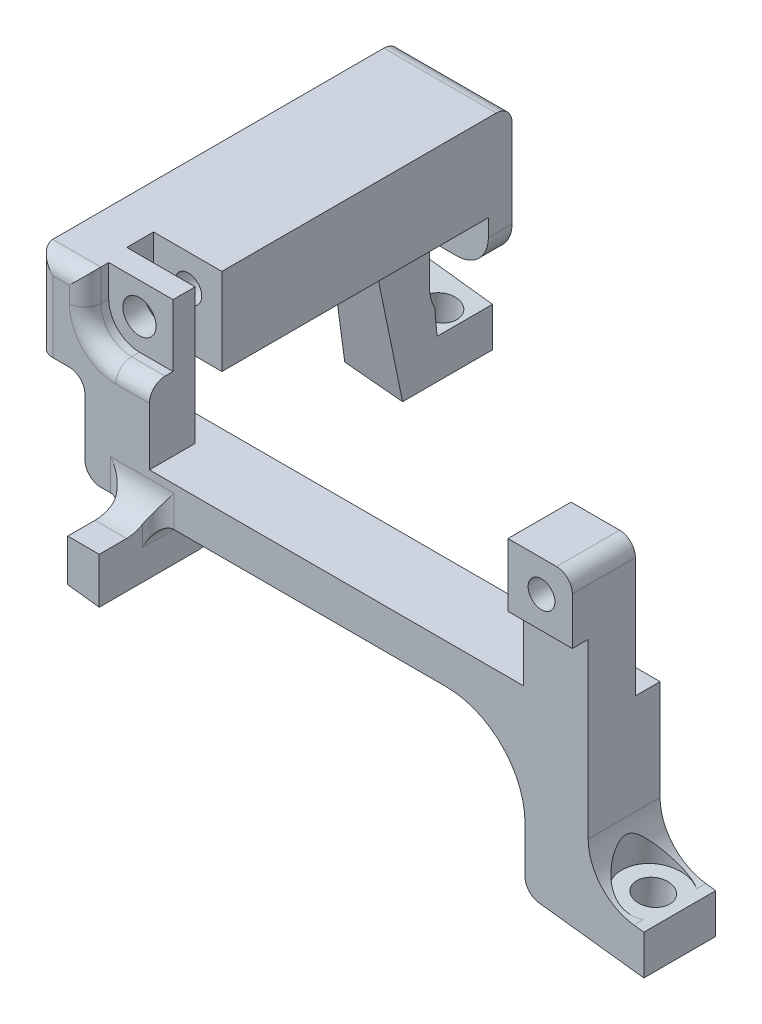
SolidWorks part; units mm, degrees
ref_plane "Front" through (0, 0, 0) normal (0, 0, 1) x (1, 0, 0)
ref_plane "Top" through (0, 0, 0) normal (0, 1, 0) x (1, 0, 0)
ref_plane "Right" through (0, 0, 0) normal (1, 0, 0) x (0, 0, -1)
sketch "Sketch1" plane through (0, 0, 0) normal (0, 0, 1) x (1, 0, 0)
  line L0 (14, 0) -> (-14, 0) construction
  line L1 (0, 0) -> (0, 9.8285) construction
  line L2 (-14, -1) -> (-16, -1)
  line L3 (-16, -1) -> (-16, -5)
  line L4 (-14.5, -6.5) -> (-10.625, -6.5)
  line L5 (-10.625, -6.5) -> (-11.575, 0)
  line L6 (-11.575, 0) -> (-10.625, 6.5)
  line L7 (-10.625, 6.5) -> (-14.5, 6.5)
  line L8 (-16, 5) -> (-16, 1)
  line L9 (-16, 1) -> (-14, 1)
  line L10 (14, 1) -> (16, 1)
  line L11 (16, 1) -> (16, 5)
  line L12 (14.5, 6.5) -> (11.575, 6.5)
  line L13 (11.575, 6.5) -> (11.575, -6.5)
  line L14 (11.575, -6.5) -> (14.5, -6.5)
  line L15 (16, -5) -> (16, -1)
  line L16 (16, -1) -> (14, -1)
  circle A0 centre (-14, -3.5) radius 1.2
  arc A1 (-14, -1) -> (-14, 1) centre (-14, 0) ccw
  arc A2 (-16, -5) -> (-14.5, -6.5) centre (-14.5, -5) ccw
  arc A3 (-14.5, 6.5) -> (-16, 5) centre (-14.5, 5) ccw
  arc A4 (14, 1) -> (14, -1) centre (14, 0) ccw
  arc A5 (16, 5) -> (14.5, 6.5) centre (14.5, 5) ccw
  arc A6 (14.5, -6.5) -> (16, -5) centre (14.5, -5) ccw
  circle A7 centre (-14, 3.5) radius 1.2
  circle A8 centre (14, 3.5) radius 1.2
  circle A9 centre (14, -3.5) radius 1.2
sketch "Sketch2" plane through (0, 0, 0) normal (0, 0, 1) x (1, 0, 0)
  line L0 (0, 9.8285) -> (0, 0) construction
  line L1 (0, 0) -> (7.7633, 0) construction
  line L2 (14, 0) -> (-14, 0) construction
  line L3 (11.8723, 2) -> (11.8723, -6.6)
  line L4 (11.8723, 2) -> (15.9561, 2)
  line L5 (15.9561, 2) -> (15.9561, -9.1)
  line L6 (11.8723, -9.1) -> (15.9561, -9.1)
  line L11 (11.575, -6.5) -> (14.5, -6.5) construction
  line L12 (-11.8723, -9.1) -> (-15.9561, -9.1)
  line L13 (-15.9561, 2) -> (-15.9561, -9.1)
  line L14 (-11.8723, 2) -> (-15.9561, 2)
  line L15 (-11.8723, 2) -> (-11.8723, -6.6)
  line L16 (-11.8723, -6.6) -> (11.8723, -6.6)
  line L17 (-11.8723, -9.1) -> (11.8723, -9.1)
  circle A5 centre (14, 0) radius 0.85
  circle A7 centre (-14, 0) radius 0.85
  point P18 (16.2195, 0)
  point P19 (11.8723, 0)
  point P24 (-11.8723, 0)
  point P25 (-16.2195, 0)
  dimension "D1" = 1.7
  dimension "D2" = 2.6
  dimension "D3" = 2
  dimension "D4" = 2.5
extrude "Boss-Extrude1" add sketch "Sketch2" along normal blind 3
sketch "Sketch4" plane through (0, 0, 3) normal (0, 0, -1) x (-1, 0, 0)
  line L4 (19, -3.5) -> (11.8723, -3.5)
  line L5 (16, 5) -> (16, 1) construction
  line L12 (-11.8723, 2) -> (-15.9561, 2)
  line L13 (-11.8723, -6.6) -> (-11.8723, 2)
  line L14 (11.8723, -6.6) -> (-11.8723, -6.6)
  line L15 (11.8723, 2) -> (11.8723, -6.6)
  line L24 (15.9561, 2) -> (11.8723, 2)
  line L25 (15.9561, -9.1) -> (15.9561, 2)
  line L26 (-15.9561, -9.1) -> (15.9561, -9.1)
  line L27 (-15.9561, 2) -> (-15.9561, -9.1)
  line L31 (11.8723, 2) -> (11.8723, -3.5)
  line L32 (19, 2) -> (11.8723, 2)
  line L33 (19, -3.5) -> (19, 2)
  circle A0 centre (14, 0) radius 0.85 construction
  circle A4 centre (14, 0) radius 0.85
  dimension "D2" = 3
  dimension "D3" = 5.5
  dimension "D1" = 0
extrude "Boss-Extrude4" add sketch "Sketch4" along normal blind 23
sketch3d "3DSketch2"
  line L1 (-16.6159, -13.7359, -29.8251) -> (-16.6279, -13.8361, -11.4071)
  line L3 (-16.8037, -15.2994, -29.8337) -> (-16.822, -15.4514, -1.8941)
  line L5 (19.1763, -18.1904, -1.8855) -> (19.1946, -18.0384, -29.825)
  line L7 (18.9885, -19.7539, -1.8941) -> (19.0068, -19.6019, -29.8337)
  line L9 (-16.822, -15.4514, -1.8941) -> (18.9885, -19.7539, -1.8941)
  line L16 (-8.1309, -12.4958, 3.3629) -> (-13.5709, -11.8396, 2.8881)
  line L17 (-13.5709, -11.8396, 2.8881) -> (-13.9941, -11.8157, 7.7697)
  line L18 (-15.0389, -16.4734, -26.8629) -> (-17.1237, -16.2231, -28.5755)
  line L19 (-17.1237, -16.2231, -28.5755) -> (-20.0144, -15.8758, -28.5736)
  line L20 (-20.0144, -15.8758, -28.5736) -> (-20.0088, -15.8758, -20.1351)
  line L21 (-20.0088, -15.8758, -20.1351) -> (-15.0342, -16.4734, -19.7009)
  line L22 (-15.0342, -16.4734, -19.7009) -> (-15.0389, -16.4734, -26.8629)
  line L23 (-13.9941, -11.8157, 7.7697) -> (-8.5541, -12.472, 8.2445)
  line L24 (-8.5541, -12.472, 8.2445) -> (-8.1309, -12.4958, 3.3629)
  line L27 (19.2027, -19.905, 2.5565) -> (19.4906, -19.9393, 2.5133)
  line L28 (19.4906, -19.9393, 2.5133) -> (19.4876, -19.891, -6.1776)
  line L29 (19.4876, -19.891, -6.1776) -> (15.5054, -19.4106, -6.5252)
  line L30 (15.5054, -19.4106, -6.5252) -> (14.7518, -19.3681, 2.1681)
  line L31 (14.7518, -19.3681, 2.1681) -> (19.2027, -19.905, 2.5565)
  circle A1 centre (-13.5979, -14.1686, -17.1253) radius 1.0922
  circle A3 centre (16.6561, -17.8736, -4.4254) radius 1.0922
  point P4 (-13.4676, -13.0842, -17.1193)
  point P13 (16.7864, -16.7892, -4.4194)
sketch "Sketch6" plane through (0, -3.5, 0) normal (0, -1, 0) x (1, 0, 0)
  line L0 (-19, -20) -> (-19, 3) construction
  line L1 (-19, -14) -> (-15, -14)
  line L3 (-17.1075, -20) -> (-15, -20)
  line L4 (-15, -14) -> (-15, -20)
  line L5 (-17.1075, -20) -> (-17.1075, -24)
  line L6 (-17.1075, -24) -> (-21.6075, -24)
  line L7 (-21.6075, -24) -> (-21.6075, -20.5)
  line L8 (-21.6075, -20.5) -> (-19, -14)
  line L9 (-11.8723, -20) -> (-19, -20) construction
  line L10 (-16.8037, -29.8337) -> (-16.822, -1.8941) construction
  dimension "D1" = 6
  dimension "D2" = 4
  dimension "D3" = 0.3
  dimension "D4" = 4
  dimension "D5" = 4.5
extrude "Boss-Extrude5" add sketch "Sketch6" along normal blind 15
sketch "Sketch7" plane through (0, 0, -20) normal (0, 0, -1) x (-1, 0, 0)
  line L2 (14.0212, -3.5) -> (15, -3.5)
  line L8 (17.1075, -18.5) -> (17.1075, -3.5) construction
  line L9 (17.1075, -16.1243) -> (21.6075, -15.5836)
  line L10 (21.6075, -18.5) -> (21.6075, -3.5) construction
  line L11 (21.6075, -15.5836) -> (23.6286, -15.5836)
  line L12 (23.6286, -15.5836) -> (23.6286, -22.5222)
  line L13 (23.6286, -22.5222) -> (10.4164, -22.2485)
  line L14 (10.4164, -22.2485) -> (14.0212, -3.5)
  line L15 (17.1237, -16.2231) -> (20.0144, -15.8758) construction
  line L16 (17.1075, -5.6075) -> (17.1075, -16.1243)
  line L17 (11.8723, -3.5) -> (15, -3.5) construction
  line L19 (19, -3.5) -> (19, 2) construction
  line L20 (21.6075, -3.5) -> (17.1075, -3.5) construction
  line L21 (21.6075, -11) -> (25.1448, -10.7901)
  line L22 (25.1448, -10.7901) -> (25.5768, -0.3222)
  line L23 (25.5768, -0.3222) -> (19, -3.5)
  arc A0 (15, -3.5) -> (17.1075, -5.6075) centre (15, -5.6075) cw
  arc A1 (19, -3.5) -> (21.6075, -11) centre (29.5908, -4.0212) ccw
  dimension "D2" = 0.1
extrude "Cut-Extrude1" cut sketch "Sketch7" against normal blind 11 and the other way through all
sketch "Sketch8" plane through (0, 0, 0) normal (0, 0, -1) x (-1, 0, 0)
  line L0 (-11.8723, -6.6) -> (11.8723, -6.6) construction
  line L1 (10.625, -6.6) -> (16.208, -6.6)
  line L2 (10.625, -6.6) -> (10.625, 7.0661)
  line L3 (10.625, 7.0661) -> (16.208, 7.0661)
  line L4 (16.208, -6.6) -> (16.208, 7.0661)
extrude "Cut-Extrude2" cut sketch "Sketch8" along normal blind 1.7 from offset 0.1 offset against normal yes
sketch "Sketch11" plane through (0, -9.1, 0) normal (0, -1, 0) x (1, 0, 0)
  line L0 (11.9561, 3) -> (11.9561, -1.5618)
  line L1 (11.9561, 3) -> (19.4908, 3)
  line L2 (19.4908, 3) -> (19.4892, -1.5618)
  line L3 (19.4906, 2.5133) -> (19.4876, -6.1776) construction
  line L4 (15.9561, 3) -> (15.9561, 0) construction
  line L5 (-15.9561, 3) -> (15.9561, 3) construction
  line L12 (19.4892, -1.5618) -> (11.9561, -1.5618)
  line L13 (-16.822, -1.8941) -> (18.9885, -1.8941) construction
  dimension "D1" = 4
extrude "Boss-Extrude7" add sketch "Sketch11" along normal blind 14
sketch "Sketch12" plane through (0, 0, 3) normal (0, 0, 1) x (1, 0, 0)
  line L0 (15.9561, -9.1) -> (15.9561, -12.9614)
  line L1 (19.4908, -23.1) -> (19.4908, -9.1) construction
  line L2 (19.4908, -16.3136) -> (22.8124, -18.7908)
  line L3 (22.8124, -18.7908) -> (22.6689, -19.2151)
  line L4 (11.9561, -17.9228) -> (22.6689, -19.2151)
  line L5 (11.9561, -23.1) -> (11.9561, -9.1) construction
  line L6 (11.9561, -17.9228) -> (9.0827, -23.6916)
  line L7 (9.0827, -23.6916) -> (17.7874, -25.7227)
  line L8 (17.7874, -25.7227) -> (28.7035, -17.0841)
  line L9 (28.7035, -17.0841) -> (21.4389, -6.27)
  line L10 (21.4389, -6.27) -> (15.9561, -9.1)
  line L12 (14.7518, -19.3681) -> (19.2027, -19.905) construction
  line L13 (19.4908, -16.3136) -> (18.8609, -16.2376)
  arc A1 (18.8609, -16.2376) -> (15.9561, -12.9614) centre (19.2561, -12.9614) cw
  dimension "D1" = 1.1
  dimension "D3" = 3.3
  dimension "D2" = 2.5
extrude "Cut-Extrude4" cut sketch "Sketch12" against normal through all
sketch "Sketch13" plane through (-1.9595, -16.2442, 0) normal (-0.1198, -0.9928, 0) x (0.9928, -0.1198, 0)
  line L0 (19.6058, 3) -> (19.6058, -1.5618) construction
  line L1 (21.6058, 3) -> (14.0165, 3) construction
  line L2 (21.6042, -1.5618) -> (14.0165, -1.5618) construction
  circle A0 centre (19.6058, 0.7191) radius 1.05
  point P9 (19.6058, 0.7191)
  dimension "D1" = 2.1
  dimension "D2" = 2
extrude "Cut-Extrude5" cut sketch "Sketch13" against normal blind 14
sketch "Sketch14" plane through (-1.6601, -13.7622, 0) normal (0.1198, 0.9928, 0) x (0.9928, -0.1198, 0)
  circle A0 centre (19.6058, -0.7191) radius 2
  dimension "D1" = 4
extrude "Cut-Extrude6" cut sketch "Sketch14" along normal blind 14
sketch "Sketch15" plane through (0, 0, 0) normal (0, 0, -1) x (-1, 0, 0)
  line L1 (-15.9561, -9.1) -> (15.9561, -9.1)
  line L2 (-15.9561, -9.1) -> (-15.9561, -6.6)
  line L3 (-15.9561, -6.6) -> (15.9561, -6.6)
  line L4 (15.9561, -9.1) -> (15.9561, -6.6)
extrude "Boss-Extrude8" add sketch "Sketch15" along normal up to vertex (1.5618 mm away) up to point (11.9561, -9.1, -1.5618)
fillet "Fillet1" radius 5 1 edges at (11.9561, -9.1, 0.7191)
sketch "Sketch16" plane through (0, 0, 3) normal (0, 0, 1) x (1, 0, 0)
  line L0 (15.9561, -12.9614) -> (15.9561, 2) construction
  line L1 (11.8723, 2) -> (15.9561, 2)
  line L2 (11.8723, 2) -> (11.8723, -2)
  line L3 (11.8723, -2) -> (15.9561, -2)
  line L4 (15.9561, 2) -> (15.9561, -2)
  circle A0 centre (14, 0) radius 0.85 construction
  circle A1 centre (14, 0) radius 0.85
  dimension "D1" = 4
extrude "Boss-Extrude9" add sketch "Sketch16" along normal blind 1
sketch "Sketch17" plane through (0, 0, 3) normal (0, 0, 1) x (1, 0, 0)
  circle A0 centre (-14, 0) radius 1.05
  dimension "D1" = 2.1
extrude "Cut-Extrude8" cut sketch "Sketch17" against normal up to vertex (2.9 mm away) up to point (-11.8723, 2, 0.1)
sketch "Sketch18" plane through (0, 0, 3) normal (0, 0, 1) x (1, 0, 0)
  line L0 (-14, -1.95) -> (-7.6767, -1.95)
  line L1 (-7.6767, -1.95) -> (-7.6767, 5.8661)
  line L2 (-7.6767, 5.8661) -> (-15.95, 5.8661)
  line L3 (-15.95, 5.8661) -> (-15.95, 0)
  arc A0 (-15.95, 0) -> (-14, -1.95) centre (-14, 0) ccw
  dimension "D1" = 3.9
extrude "Cut-Extrude9" cut sketch "Sketch18" against normal blind 1.5
sketch "Sketch19" plane through (0, -9.1, 0) normal (0, -1, 0) x (1, 0, 0)
  line L0 (-13.3228, -1.5618) -> (-13.3228, 6.7295)
  line L1 (-13.3228, 6.7295) -> (-11.3228, 6.7295)
  line L2 (-11.3228, 6.7295) -> (-11.3228, -1.5618)
  line L3 (-11.3228, -1.5618) -> (-13.3228, -1.5618)
  line L4 (6.9561, -1.5618) -> (-15.9561, -1.5618) construction
  dimension "D1" = 2
extrude "Boss-Extrude10" add sketch "Sketch19" along normal blind 4
sketch "Sketch20" plane through (0, 0, 6.7295) normal (0, 0, 1) x (1, 0, 0)
  line L0 (-14.1028, -11.6747) -> (-9.3852, -12.2438)
  line L1 (-9.3852, -12.2438) -> (-9.3852, -14.5443)
  line L2 (-9.3852, -14.5443) -> (-14.449, -14.5443)
  line L3 (-14.449, -14.5443) -> (-14.1028, -11.6747)
  line L4 (-8.1309, -12.4958) -> (-13.5709, -11.8396) construction
  dimension "D1" = 0.1
extrude "Cut-Extrude10" cut sketch "Sketch20" against normal blind 9
fillet "Fillet2" radius 2 2 edges at (-12.3228, -11.8895, -1.5618) (-12.3228, -9.1, 3)
fillet "Fillet3" radius 1 4 edges at (-13.3228, -8.1, 3) (-11.3228, -8.1, 3) (-11.3228, -9.1, 0.7191) (-13.3228, -9.1, 0.7191)
sketch "Sketch23" plane through (-21.6075, 0, 0) normal (-1, 0, 0) x (0, 0, 1)
  line L0 (-20, 2) -> (-20, -10.0836)
  line L1 (-23, -13.0836) -> (-24, -13.0836)
  line L2 (-24, -15.5836) -> (-24, -11) construction
  line L3 (-24, -13.0836) -> (-30.6646, -1.3599)
  line L4 (-30.6646, -1.3599) -> (-20, 2)
  arc A0 (-20, -10.0836) -> (-23, -13.0836) centre (-23, -10.0836) cw
  dimension "D1" = 3
  dimension "D2" = 2.5
extrude "Cut-Extrude11" cut sketch "Sketch23" along direction (0.9929, -0.1193, 0) on the side against the normal blind 9
sketch "Sketch24" plane through (-1.857, -15.4566, 0) normal (0.1193, 0.9929, 0) x (0.9929, -0.1193, 0)
  line L0 (-17.9734, 22) -> (-15.3602, 22) construction
  line L2 (-15.3602, 24) -> (-15.3602, 23) construction
  line L4 (-15.3602, 24) -> (-19.8925, 24) construction
  line L5 (-17.9777, 28.5736) -> (-17.9722, 20.1351) construction
  circle A0 centre (-16.6668, 22) radius 1.05
  point P10 (-16.6668, 22)
  dimension "D1" = 2.1
  dimension "D2" = 2
extrude "Cut-Extrude13" cut sketch "Sketch24" against normal blind 9
sketch "Sketch25" plane through (-1.857, -15.4566, 0) normal (0.1193, 0.9929, 0) x (0.9929, -0.1193, 0)
  circle A0 centre (-16.6668, 22) radius 2
  arc A1 (-16.3466, 23) -> (-16.9869, 23) centre (-16.6668, 22) ccw construction
  dimension "D1" = 4
extrude "Cut-Extrude14" cut sketch "Sketch25" along normal blind 9
sketch "Sketch26" plane through (-17.1075, 0, 0) normal (1, 0, 0) x (0, 0, -1)
  line L1 (14, -16.1243) -> (24, -16.1243) construction
  line L4 (12.5998, -17.6786) -> (18.2966, -16.1243)
  line L6 (18.2966, -16.1243) -> (15.6937, -3.5)
  line L7 (20, -3.5) -> (14, -3.5) construction
  line L8 (15.6937, -3.5) -> (13.321, -3.5)
  line L9 (20, -3.5) -> (1.6, -3.5) construction
  line L10 (13.321, -3.5) -> (12.5998, -17.6786)
extrude "Cut-Extrude15" cut sketch "Sketch26" against normal blind 9 and the other way blind 9
sketch "Sketch27" plane through (-19, 0, 0) normal (-1, 0, 0) x (0, 0, 1)
  line L0 (-17.5881, -0.75) -> (0.3127, -0.75) construction
  line L1 (-17.5881, 0.75) -> (0.3127, 0.75)
  line L2 (-17.5881, -2.25) -> (0.3127, -2.25)
  line L3 (-20, -3.5) -> (-20, 2) construction
  arc A0 (-17.5881, 0.75) -> (-17.5881, -2.25) centre (-17.5881, -0.75) ccw
  arc A1 (0.3127, -2.25) -> (0.3127, 0.75) centre (0.3127, -0.75) ccw
  point P2 (-8.6377, -0.75)
  point P9 (-20, -0.75)
  dimension "D1" = 3
extrude "Cut-Extrude16" cut sketch "Sketch27" against normal blind 2
sketch "Sketch28" plane through (0, -3.5, 0) normal (0, -1, 0) x (1, 0, 0)
  line L0 (-17.1075, -20) -> (-17.1075, -16.1282) construction
  line L1 (-11.8723, -20) -> (-17.1075, -20)
  line L2 (-11.8723, -20) -> (-11.8723, -18.5)
  line L3 (-11.8723, -18.5) -> (-17.1075, -18.5)
  line L4 (-17.1075, -20) -> (-17.1075, -18.5)
  dimension "D1" = 1.5
extrude "Boss-Extrude11" add sketch "Sketch28" along normal up to vertex (3.1 mm away) up to point (-15.9561, -6.6, -1.5618)
fillet "Fillet4" radius 1 4 edges at (-17, 0.75, -8.6377) (-17, -0.75, 1.8127) (-17, -2.25, -8.6377) (-17, -0.75, -19.0881)
fillet "Fillet5" radius 1 4 edges at (-15.9561, -3.5, 1.55) (-15.9561, -7.85, -1.5618) (-15.9561, -9.1, 0.7191) (-17, -3.5, -15.6937)
fillet "Fillet6" radius 1 8 edges at (-15.95, 1, 3) (-12.9362, -1.95, 3) (-15.3789, -1.3789, 3) (11.9561, -17.9228, 0.7191) (15.9561, 2, 2) (-17.475, 2, 3) (-19, -0.75, 3) (-15.4362, 2, -20)
fillet "Fillet7" radius 2 1 edges at (-11.8723, -6.6, -19.25)
fillet "Fillet8" radius 2 1 edges at (-17.1075, -6.6, -19.25)
